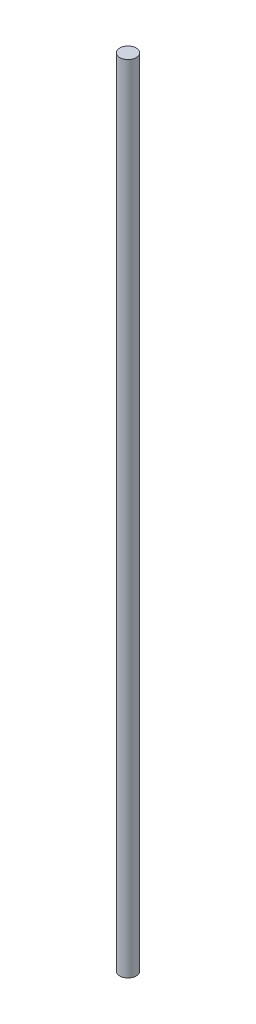
SolidWorks part; units mm, degrees
ref_plane "Front Plane" through (0, 0, 0) normal (0, 0, 1) x (1, 0, 0)
ref_plane "Top Plane" through (0, 0, 0) normal (0, 1, 0) x (1, 0, 0)
ref_plane "Right Plane" through (0, 0, 0) normal (1, 0, 0) x (0, 0, -1)
sketch "Sketch1" plane through (0, 0, 0) normal (0, 1, 0) x (1, 0, 0)
  circle A0 centre (0, 0) radius 3.175
extrude "Boss-Extrude1" add sketch "Sketch1" along normal blind 304.8
